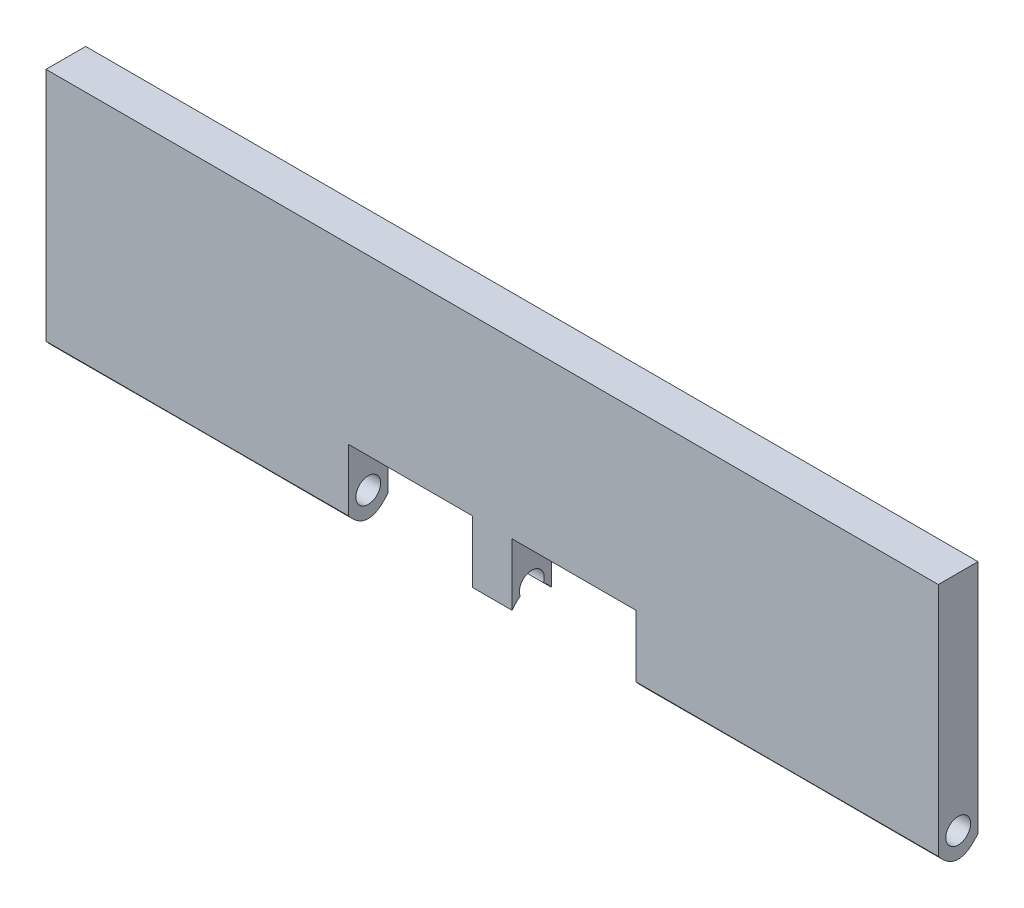
SolidWorks part; units mm, degrees
ref_plane "Plan de face" through (0, 0, 0) normal (0, 0, 1) x (1, 0, 0)
ref_plane "Plan de dessus" through (0, 0, 0) normal (0, 1, 0) x (1, 0, 0)
ref_plane "Plan de droite" through (0, 0, 0) normal (1, 0, 0) x (0, 0, -1)
sketch "Esquisse1" plane through (0, 0, 0) normal (0, 0, 1) x (1, 0, 0)
  line L0 (-29, -25) -> (-29, -10)
  line L1 (-90, -25) -> (-29, -25)
  line L2 (-90, -25) -> (-90, 25)
  line L3 (-90, 25) -> (90, 25)
  line L4 (90, -25) -> (90, 25)
  line L5 (-90, -25) -> (90, 25) construction
  line L6 (-90, 25) -> (90, -25) construction
  line L7 (-29, -10) -> (-4, -10)
  line L8 (-4, -10) -> (-4, -25)
  line L9 (0, 0) -> (0, -25) construction
  line L10 (-4, -25) -> (4, -25)
  line L11 (4, -10) -> (4, -25)
  line L12 (29, -10) -> (4, -10)
  line L13 (29, -25) -> (29, -10)
  line L14 (29, -25) -> (90, -25)
  point P0 (0, 0)
  dimension "D1" = 180
  dimension "D2" = 50
  dimension "D3" = 25
  dimension "D4" = 4
  dimension "D5" = 15
extrude "Boss.-Extru.1" add sketch "Esquisse1" along normal blind 8
sketch "Esquisse2" plane through (-90, 0, 0) normal (-1, 0, 0) x (0, 0, 1)
  line L0 (4, -25) -> (4, -8.5674) construction
  line L1 (8, -25) -> (0, -25) construction
  line L2 (4, -22.5) -> (0, -22.5) construction
  line L3 (0, 25) -> (0, -25) construction
  line L4 (8, 25) -> (8, -25) construction
  line L5 (0, -22.5) -> (0, -25)
  line L6 (0, -25) -> (8, -25)
  line L7 (8, -25) -> (8, -22.5)
  circle A0 centre (4, -20) radius 2.5
  spline S0 degree 2 poles (0, -22.5) (4, -27.5) (8, -22.5) knots 0 0 0 1 1 1
  line M1 (0, 25) -> (0, -25)
  line M2 (0, -25) -> (8, -25)
  line M3 (8, -25) -> (8, 25)
  dimension "D1" = 5
  dimension "D2" = 5
extrude "Enlèv. mat.-Extru.1" cut sketch "Esquisse2" against normal up to surface (180 mm away) contours S0 L6 M3 | S0 M1 M2 | A0 region at (-90, -24.25, 1) region at (-90, -24.25, 7) region at (-90, -20, 4) up to face at (90, 0, 4)
sketch "Esquisse4" plane through (0, 0, 0) normal (1, 0, 0) x (0, 0, -1)
  line L0 (0, 0) -> (5, 0) construction
  line L1 (5, 4.5) -> (0, 4.5)
  line L2 (0, 25) -> (0, -22.5) construction
  line L3 (5, -4.5) -> (0, -4.5)
  line L4 (0, 4.5) -> (0, -4.5)
  circle A0 centre (5, 0) radius 2.5
  arc A1 (5, -4.5) -> (5, 4.5) centre (5, 0) ccw
  dimension "D1" = 5
  dimension "D2" = 2
  dimension "D3" = 5
extrude "Boss.-Extru.2" add sketch "Esquisse4" along normal blind 2.5 and the other way blind 2.5
sketch "Esquisse6" plane through (-4, 0, 0) normal (-1, 0, 0) x (0, 0, 1)
  parabola Q0 (8, -22.5) -> (0, -22.5) focus (4, -23.4) apex (4, -25) construction
  parabola Q1 (0, -22.5) -> (8, -22.5) focus (4, -23.4) apex (4, -25) construction
  spline S0 degree 2 poles (0, -22.5) (4, -17.5) (8, -22.5) knots 0 0 0 1 1 1
  spline S1 degree 2 poles (0, -22.5) (4, -27.5) (8, -22.5) knots 0 0 0 1 1 1
  point P0 (4, -20)
extrude "Enlèv. mat.-Extru.2" cut sketch "Esquisse6" against normal up to surface (8 mm away) up to face at (4, -22.5, 4)
